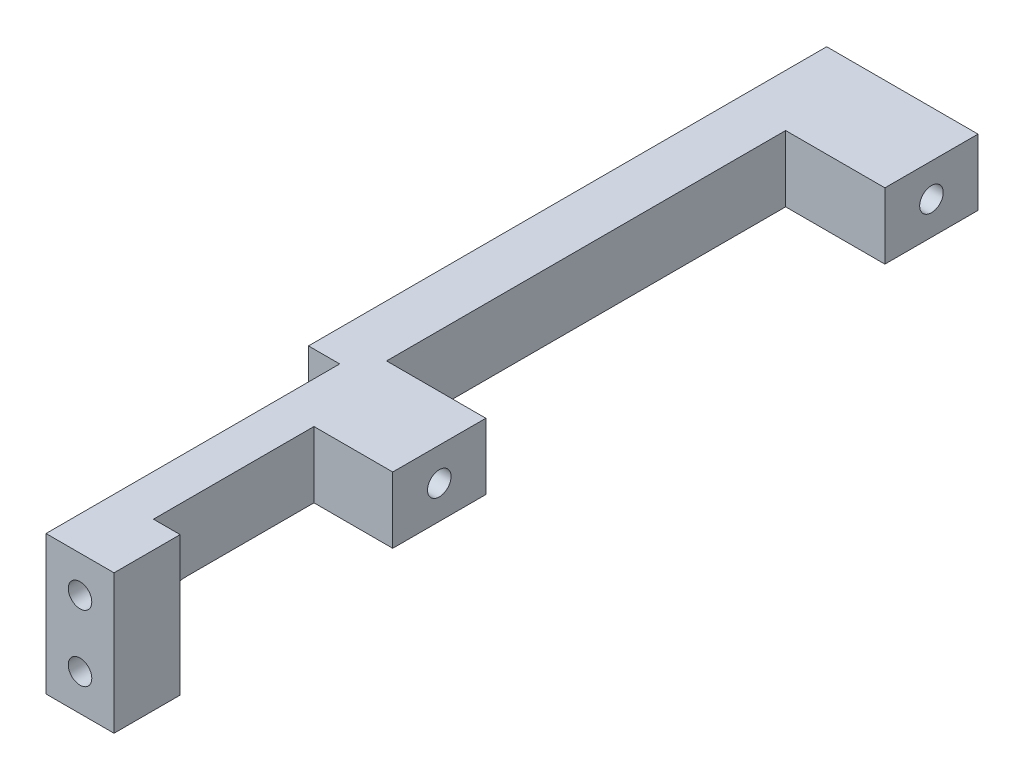
SolidWorks part; units mm, degrees
ref_plane "Front" through (0, 0, 0) normal (0, 0, 1) x (1, 0, 0)
ref_plane "Top" through (0, 0, 0) normal (0, 1, 0) x (1, 0, 0)
ref_plane "Right" through (0, 0, 0) normal (1, 0, 0) x (0, 0, -1)
sketch "Sketch1" plane through (0, 0, 0) normal (0, 1, 0) x (1, 0, 0)
  line L1 (-5.7672, 38.989) -> (5.7672, 38.989)
  line L2 (-5.7672, 38.989) -> (-5.7672, -38.989)
  line L3 (-5.7672, -38.989) -> (5.7672, -38.989)
  line L4 (5.7672, 38.989) -> (5.7672, -38.989)
  line L5 (-5.7672, 38.989) -> (5.7672, -38.989) construction
  line L6 (-5.7672, -38.989) -> (5.7672, 38.989) construction
  point P0 (0, 0)
  dimension "D1" = 77.978
  dimension "D2" = 11.5344
extrude "Boss-Extrude1" add sketch "Sketch1" along normal blind 6.35
hole_wizard "#4-40 Tapped Hole1" positions "Sketch3" profile "Sketch4" tap size "#4-40" standard "ANSI Inch"
sketch "Sketch3" plane through (5.7672, 0, 0) normal (1, 0, 0) x (0, 0, -1)
  line L0 (34.5186, 3.175) -> (-12.7508, 3.175)
  line L2 (38.989, 6.35) -> (38.989, 0) construction
  line L3 (38.989, 6.35) -> (34.5186, 3.175)
  line L6 (34.5186, 3.175) -> (38.989, 0)
  point P0 (34.5186, 3.175)
  point P2 (-12.7508, 3.175)
  dimension "D1" = 47.2694
  dimension "D2" = 4.4704
cosmetic thread "Hole Thread1" parameters "D1"=6.096, "D2"=2.8448
cosmetic thread "Hole Thread2" parameters "D1"=6.096, "D2"=2.8448
sketch "Sketch4" plane through (5.7672, 3.175, -34.5186) normal (0, 1, 0) x (0, 0, -1)
  line L0 (0, 0) -> (0, 7.0292)
  line L1 (0, 7.0292) -> (1.1303, 6.35)
  line L2 (1.1303, 6.35) -> (1.1303, 0)
  line L5 (1.1303, 0) -> (0, 0)
  line L10 (0, 7.0292) -> (-1.1303, 6.35) construction
  line L11 (0, -6.35) -> (0, 107.95) construction
  dimension "Tap Drill Dia." = 2.2606
  dimension "Tap Drill Depth" = 6.35
  dimension "Drill Angle" = 118
sketch "Sketch2" plane through (0, 6.35, 0) normal (0, 1, 0) x (1, 0, 0)
  line L0 (5.7672, -38.989) -> (5.7672, 38.989) construction
  line L1 (-3.7672, 30.0482) -> (5.7672, 30.0482)
  line L2 (-3.7672, 30.0482) -> (-3.7672, -8.2804)
  line L3 (-3.7672, -8.2804) -> (5.7672, -8.2804)
  line L4 (5.7672, 30.0482) -> (5.7672, -8.2804)
  line L5 (-3.7672, 30.0482) -> (5.7672, -8.2804) construction
  line L6 (-3.7672, -8.2804) -> (5.7672, 30.0482) construction
  line L7 (5.7672, 33.3883) -> (5.7672, 35.6489) construction
  line L8 (-1.7985, -32.639) -> (5.7672, -32.639)
  line L9 (-1.7985, -32.639) -> (-1.7985, -17.2212)
  line L10 (-1.7985, -17.2212) -> (5.7672, -17.2212)
  line L11 (5.7672, -32.639) -> (5.7672, -17.2212)
  line L12 (-1.7985, -32.639) -> (5.7672, -17.2212) construction
  line L13 (-1.7985, -17.2212) -> (5.7672, -32.639) construction
  line L14 (5.7672, 33.3883) -> (5.7672, 35.6489) construction
  line L15 (5.7672, 35.6489) -> (5.7672, 38.989) construction
  line L16 (5.7672, 33.3883) -> (5.7672, 30.0482) construction
  line L17 (5.7672, 33.3883) -> (5.7672, 35.6489) construction
  line L19 (5.7672, -13.8811) -> (5.7672, -11.6205) construction
  line L20 (5.7672, -13.8811) -> (5.7672, -11.6205) construction
  line L21 (5.7672, -11.6205) -> (5.7672, -8.2804) construction
  line L22 (5.7672, -13.8811) -> (5.7672, -17.2212) construction
  line L23 (-5.7672, 38.989) -> (-5.7672, -38.989) construction
  line L24 (-5.7672, -38.989) -> (5.7672, -38.989) construction
  point P0 (1, 10.8839)
  point P8 (1.9844, -24.9301)
  dimension "D1" = 2
  dimension "D2" = 3.9688
  dimension "D3" = 6.35
extrude "Cut-Extrude1" cut sketch "Sketch2" against normal through all
sketch "Sketch8" plane through (0, 6.35, 0) normal (0, 1, 0) x (1, 0, 0)
  line L1 (0.7672, -38.989) -> (5.7672, -38.989)
  line L2 (0.7672, -38.989) -> (0.7672, -32.639)
  line L3 (0.7672, -32.639) -> (5.7672, -32.639)
  line L4 (5.7672, -38.989) -> (5.7672, -32.639)
  line L5 (0.7672, -38.989) -> (5.7672, -32.639) construction
  line L6 (0.7672, -32.639) -> (5.7672, -38.989) construction
  point P0 (3.2672, -35.814)
  dimension "D1" = 5
extrude "Cut-Extrude2" cut sketch "Sketch8" against normal through all
sketch "Sketch9" plane through (0, 0, 38.989) normal (0, 0, 1) x (1, 0, 0)
  line L1 (-5.7672, -7) -> (0.7672, -7)
  line L2 (-5.7672, -7) -> (-5.7672, 0)
  line L3 (-5.7672, 0) -> (0.7672, 0)
  line L4 (0.7672, -7) -> (0.7672, 0)
  line L5 (-5.7672, -7) -> (0.7672, 0) construction
  line L6 (-5.7672, 0) -> (0.7672, -7) construction
  point P0 (-2.5, -3.5)
  dimension "D1" = 7
extrude "Boss-Extrude2" add sketch "Sketch9" against normal up to surface (6.35 mm away) up to face at (-0.5156, 3.175, 32.639)
hole_wizard "#4-40 Tapped Hole2" positions "Sketch5" profile "Sketch7" tap size "#4-40" standard "ANSI Inch"
sketch "Sketch5" plane through (0, 0, 38.989) normal (0, 0, 1) x (1, 0, 0)
  line L0 (-5.7672, 6.35) -> (-2.5, 2.85) construction
  line L1 (-2.5, 2.85) -> (-2.5, -3.5) construction
  line L2 (-2.5, -3.5) -> (0.7672, -7) construction
  line L4 (-2.5, -3.5) -> (-5.7672, -7) construction
  line L5 (-2.5, 2.85) -> (0.7672, 6.35) construction
  line L6 (-5.7672, 6.35) -> (0.7672, 6.35) construction
  point P0 (-2.5, 2.85)
  point P2 (-2.5, -3.5)
  dimension "D1" = 3.5
sketch "Sketch7" plane through (-2.5, 2.85, 38.989) normal (1, 0, 0) x (0, -1, 0)
  line L0 (0, 0) -> (0, 5.6792)
  line L1 (0, 5.6792) -> (1.1303, 5)
  line L2 (1.1303, 5) -> (1.1303, 0)
  line L5 (1.1303, 0) -> (0, 0)
  line L10 (0, 5.6792) -> (-1.1303, 5) construction
  line L11 (0, -6.35) -> (0, 107.95) construction
  dimension "Tap Drill Dia." = 2.2606
  dimension "Tap Drill Depth" = 5
  dimension "Drill Angle" = 118
cosmetic thread "Hole Thread4" parameters "D1"=5, "D2"=2.8448
cosmetic thread "Hole Thread5" parameters "D1"=5, "D2"=2.8448
sketch "Sketch10" plane through (0, 0, 0) normal (0, -1, 0) x (1, 0, 0)
  line L0 (-5.7672, -38.989) -> (-5.7672, 32.639) construction
  line L1 (-8.7672, 10.7804) -> (-5.7672, 10.7804)
  line L2 (-8.7672, 10.7804) -> (-8.7672, -38.989)
  line L3 (-8.7672, -38.989) -> (-5.7672, -38.989)
  line L4 (-5.7672, 10.7804) -> (-5.7672, -38.989)
  line L5 (-8.7672, 10.7804) -> (-5.7672, -38.989) construction
  line L6 (-8.7672, -38.989) -> (-5.7672, 10.7804) construction
  line L8 (-3.7672, 8.2804) -> (5.7672, 8.2804) construction
  point P0 (-7.2672, -14.1043)
  dimension "D1" = 3
  dimension "D2" = 2.5
extrude "Boss-Extrude3" add sketch "Sketch10" against normal up to surface (6.35 mm away) up to face at (0.1615, 6.35, 4.6821)
fillet "Fillet1" radius 3.175 1 edges at (-3.7828, 0, 32.639)
